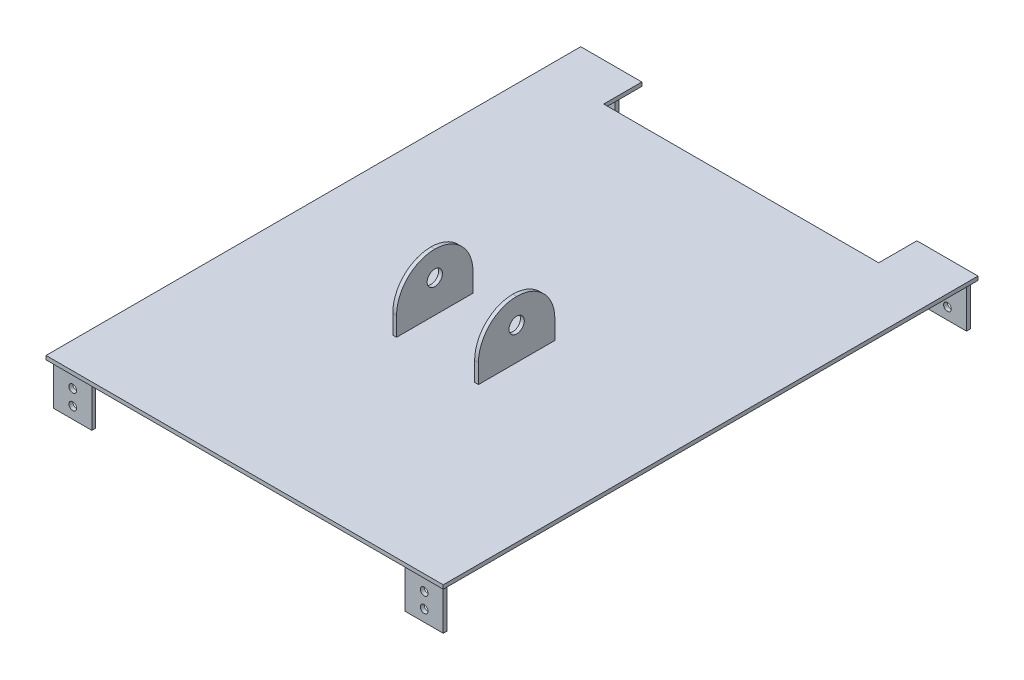
SolidWorks part; units mm, degrees
ref_plane "Front Plane" through (0, 0, 0) normal (0, 0, 1) x (1, 0, 0)
ref_plane "Top Plane" through (0, 0, 0) normal (0, 1, 0) x (1, 0, 0)
ref_plane "Right Plane" through (0, 0, 0) normal (1, 0, 0) x (0, 0, -1)
sketch "Sketch1" plane through (0, 0, 0) normal (0, 1, 0) x (1, 0, 0)
  line L1 (52, -70) -> (-52, -70)
  line L2 (52, -70) -> (52, 70)
  line L3 (52, 70) -> (-52, 70)
  line L4 (-52, -70) -> (-52, 70)
  line L5 (52, -70) -> (-52, 70) construction
  line L6 (52, 70) -> (-52, -70) construction
  point P0 (0, 0)
  dimension "D1" = 104
  dimension "D2" = 140
extrude "Boss-Extrude1" add sketch "Sketch1" along normal blind 1 contours L2 L1 L4 L3
sketch "Sketch2" plane through (0, 1, 0) normal (0, 1, 0) x (1, 0, 0)
  line L0 (-52, 0) -> (52, 0) construction
  line L1 (-52, -70) -> (-52, 70) construction
  line L2 (52, -70) -> (52, 70) construction
  line L3 (0, 0) -> (0, -70) construction
  line L4 (52, -70) -> (-52, -70) construction
  line L5 (-10.2198, -20) -> (-10.2198, -70) construction
  line L6 (11.2198, -20) -> (11.2198, -70) construction
  line L7 (-11.2198, 0) -> (-10.2198, 0)
  line L8 (11.2198, -20) -> (10.2198, -20)
  line L9 (11.2198, -20) -> (11.2198, 0)
  line L10 (11.2198, 0) -> (10.2198, 0)
  line L11 (10.2198, -20) -> (10.2198, 0)
  line L12 (11.2198, -20) -> (10.2198, 0) construction
  line L13 (11.2198, 0) -> (10.2198, -20) construction
  line L14 (-10.2198, -20) -> (-10.2198, 0)
  line L15 (-11.2198, -20) -> (-10.2198, -20)
  line L16 (-11.2198, -20) -> (-11.2198, 0)
  point P13 (10.7198, -10)
  dimension "D1" = 1
  dimension "D2" = 20
  dimension "D3" = 50
extrude "Boss-Extrude2" add sketch "Sketch2" along normal blind 15
sketch "Sketch6" plane through (11.2198, 0, 0) normal (1, 0, 0) x (0, 0, -1)
  line L0 (-10, 16) -> (-10, 1) construction
  line L1 (-20, 16) -> (0, 16) construction
  line L2 (-20, 1) -> (0, 1) construction
  line L3 (-20, 9.5) -> (0, 9.5) construction
  line L4 (-20, 16) -> (-20, 1) construction
  line L5 (0, 16) -> (0, 1) construction
  circle A0 centre (-10, 9.5) radius 2
  dimension "D2" = 4
  dimension "D1" = 6.5
extrude "Cut-Extrude1" cut sketch "Sketch6" against normal blind 30
fillet "Fillet3" radius 10 1 edges at (10.7198, 16, 20) type face fillet first side face at (10.7198, 16, 10) second side face at (10.7198, 8.5, 20)
fillet "Fillet4" radius 10 1 edges at (10.7198, 16, 0) type face fillet first side face at (10.7198, 16, 5) second side face at (10.7198, 8.5, 0)
fillet "Fillet5" radius 10 1 edges at (-10.7198, 16, 20) type face fillet first side face at (-10.7198, 16, 10) second side face at (-10.7198, 8.5, 20)
fillet "Fillet6" radius 10 1 edges at (-10.7198, 16, 0) type face fillet first side face at (-10.7198, 16, 5) second side face at (-10.7198, 8.5, 0)
sketch "Sketch9" plane through (0, 0, 0) normal (0, -1, 0) x (1, 0, 0)
  line L4 (-51, 69) -> (-41, 69)
  line L5 (-41, 69) -> (-41, 68)
  line L6 (-41, 68) -> (-51, 68)
  line L7 (-51, 68) -> (-51, 69)
  line L8 (-51, -69) -> (51, -69)
  line L9 (51, -69) -> (51, 69)
  line L10 (51, 69) -> (-51, 69)
  line L11 (-51, 69) -> (-51, -69)
  line L12 (-51, -69) -> (51, -69)
  line L13 (51, -69) -> (51, 69)
  line L14 (51, 69) -> (-51, 69)
  line L15 (-51, 69) -> (-51, -69)
  line L16 (0, 69) -> (0, -69) construction
  line L17 (51, 68) -> (51, 69)
  line L18 (41, 69) -> (41, 68)
  line L19 (51, 69) -> (41, 69)
  line L20 (41, 68) -> (51, 68)
  line L21 (-51, 0) -> (51, 0) construction
  line L22 (51, -68) -> (51, -69)
  line L23 (41, -68) -> (51, -68)
  line L24 (41, -69) -> (41, -68)
  line L25 (51, -69) -> (41, -69)
  line L26 (-51, -68) -> (-51, -69)
  line L27 (-41, -68) -> (-51, -68)
  line L28 (-51, -69) -> (-41, -69)
  line L29 (-41, -69) -> (-41, -68)
  line L30 (-51, -68) -> (-51, -69)
  line L31 (-41, -68) -> (-51, -68)
  line L32 (-41, -69) -> (-41, -68)
  line L33 (-51, -69) -> (-41, -69)
  line L34 (51, -68) -> (51, -69)
  line L35 (41, -68) -> (51, -68)
  line L36 (41, -69) -> (41, -68)
  line L37 (51, -69) -> (41, -69)
  dimension "D2" = 1
  dimension "D3" = 10
  dimension "D1" = 1
extrude "Boss-Extrude5" add sketch "Sketch9" along normal blind 11 contours L24 L12 L13 L23 | L12 L29 L27 L15 | L4 L5 L6 L7 | L19 L18 L20 L17 region at (-46, 0, -68.5) region at (46, 0, -68.5)
sketch "Sketch10" plane through (0, 0, -69) normal (0, 0, -1) x (-1, 0, 0)
  line L0 (46, -11) -> (46, 0) construction
  line L1 (51, -11) -> (41, -11) construction
  line L2 (51, 0) -> (41, 0) construction
  circle A0 centre (46, -8) radius 1
  circle A1 centre (46, -4) radius 1
  dimension "D1" = 4
  dimension "D2" = 2
  dimension "D4" = 2
  dimension "D3" = 3
extrude "Cut-Extrude2" cut sketch "Sketch10" against normal through all
sketch "Sketch11" plane through (0, 0, -69) normal (0, 0, -1) x (-1, 0, 0)
  line L0 (0, 0) -> (0, 0.9991) construction
sketch "Sketch12" plane through (0, 0, 69) normal (0, 0, 1) x (1, 0, 0)
  line L0 (46, 0) -> (46, -11) construction
  line L1 (51, 0) -> (41, 0) construction
  line L2 (51, -11) -> (41, -11) construction
  line L3 (52, 0) -> (-52, 0) construction
  circle A0 centre (46, -4) radius 1
  circle A1 centre (46, -8) radius 1
  dimension "D2" = 2
  dimension "D4" = 2
  dimension "D1" = 3
  dimension "D3" = 4
extrude "Cut-Extrude3" cut sketch "Sketch12" against normal through all
sketch "Sketch13" plane through (0, 1, 0) normal (0, 1, 0) x (1, 0, 0)
  line L0 (0, 70) -> (-36, 70)
  line L1 (52, 70) -> (-52, 70) construction
  line L2 (-36, 70) -> (-36, 60)
  line L3 (-36, 60) -> (36, 60)
  line L4 (36, 60) -> (36, 70)
  line L5 (36, 70) -> (0, 70)
  dimension "D1" = 36
  dimension "D2" = 36
  dimension "D3" = 10
extrude "Cut-Extrude4" cut sketch "Sketch13" against normal blind 12
